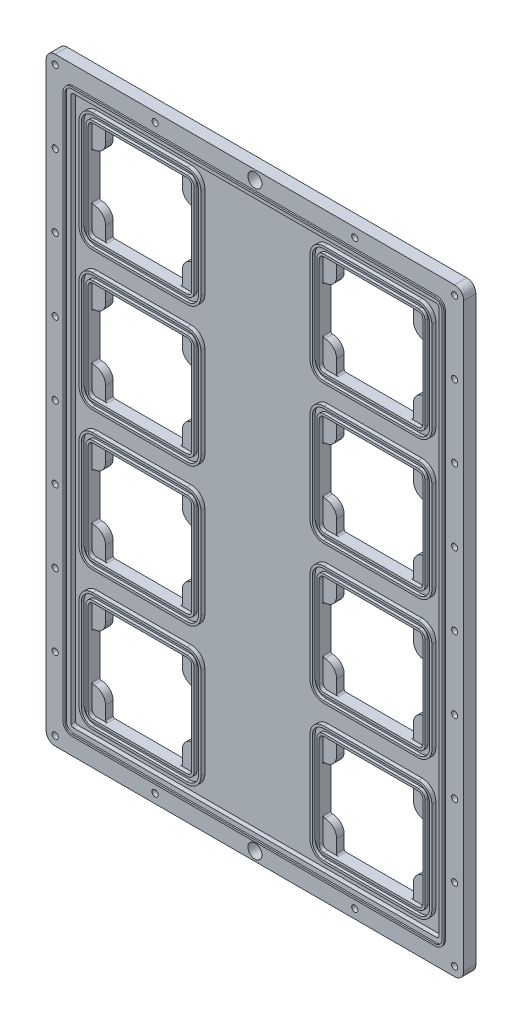
SolidWorks part; units mm, degrees
ref_plane "Front Plane" through (0, 0, 0) normal (0, 0, 1) x (1, 0, 0)
ref_plane "Top Plane" through (0, 0, 0) normal (0, 1, 0) x (1, 0, 0)
ref_plane "Right Plane" through (0, 0, 0) normal (1, 0, 0) x (0, 0, -1)
sketch "Sketch1" plane through (0, 0, 0) normal (0, 0, 1) x (1, 0, 0)
  line L1 (0, 0) -> (292.1, 0)
  line L2 (0, 0) -> (0, 419.1)
  line L3 (0, 419.1) -> (292.1, 419.1)
  line L4 (292.1, 0) -> (292.1, 419.1)
  dimension "D1" = 419.1
  dimension "D2" = 292.1
extrude "Boss-Extrude1" add sketch "Sketch1" along normal blind 8.509
sketch "Sketch4" plane through (0, 0, 8.509) normal (0, 0, 1) x (1, 0, 0)
  line L3 (0, 419.1) -> (0, 0) construction
  line L4 (6.35, 412.75) -> (285.75, 412.75) construction
  line L5 (6.35, 412.75) -> (6.35, 6.35) construction
  line L6 (6.35, 6.35) -> (285.75, 6.35) construction
  line L7 (285.75, 412.75) -> (285.75, 6.35) construction
  line L8 (292.1, 419.1) -> (0, 419.1) construction
  line L9 (292.1, 0) -> (292.1, 419.1) construction
  line L10 (0, 0) -> (292.1, 0) construction
  circle A0 centre (6.35, 6.35) radius 2.1526
  circle A1 centre (6.35, 412.75) radius 2.1526
  circle A2 centre (285.75, 412.75) radius 2.1526
  circle A3 centre (285.75, 6.35) radius 2.1526
  dimension "D5" = 4.3053
  dimension "D1" = 6.35
  dimension "D2" = 6.35
  dimension "D3" = 6.35
  dimension "D4" = 6.35
extrude "Cut-Extrude1" cut sketch "Sketch4" against normal through all
pattern_linear "LPattern2" count 8 spacing 50.8 along (0, -1, 0) of face at (287.9026, 412.75, 0) of face at (8.5026, 412.75, 0)
pattern_linear "LPattern3" count 4 spacing 69.85 along (-1, 0, 0) of face at (287.9026, 412.75, 0) of face at (287.9026, 6.35, 0)
sketch "Sketch5" plane through (0, 0, 8.509) normal (0, 0, 1) x (1, 0, 0)
  line L0 (0, 419.1) -> (0, 0) construction
  line L1 (19.05, 406.4) -> (273.05, 406.4) construction
  line L2 (12.7, 400.05) -> (12.7, 19.05) construction
  line L3 (19.05, 12.7) -> (273.05, 12.7) construction
  line L4 (279.4, 400.05) -> (279.4, 19.05) construction
  line L5 (292.1, 419.1) -> (0, 419.1) construction
  line L6 (292.1, 0) -> (292.1, 419.1) construction
  line L7 (0, 0) -> (292.1, 0) construction
  line L8 (19.05, 14.2875) -> (273.05, 14.2875) construction
  line L9 (14.2875, 400.05) -> (14.2875, 19.05) construction
  line L10 (19.05, 404.8125) -> (273.05, 404.8125) construction
  line L11 (277.8125, 400.05) -> (277.8125, 19.05) construction
  line L12 (12.827, 400.05) -> (12.827, 19.05)
  line L13 (19.05, 406.273) -> (273.05, 406.273)
  line L14 (279.273, 400.05) -> (279.273, 19.05)
  line L15 (19.05, 12.827) -> (273.05, 12.827)
  line L16 (277.9395, 400.05) -> (277.9395, 19.05)
  line L17 (19.05, 404.9395) -> (273.05, 404.9395)
  line L18 (14.1605, 400.05) -> (14.1605, 19.05)
  line L19 (19.05, 14.1605) -> (273.05, 14.1605)
  arc A0 (273.05, 12.7) -> (279.4, 19.05) centre (273.05, 19.05) ccw construction
  arc A1 (12.7, 19.05) -> (19.05, 12.7) centre (19.05, 19.05) ccw construction
  arc A2 (273.05, 406.4) -> (279.4, 400.05) centre (273.05, 400.05) cw construction
  arc A3 (19.05, 406.4) -> (12.7, 400.05) centre (19.05, 400.05) ccw construction
  arc A4 (14.2875, 19.05) -> (19.05, 14.2875) centre (19.05, 19.05) ccw construction
  arc A5 (19.05, 404.8125) -> (14.2875, 400.05) centre (19.05, 400.05) ccw construction
  arc A6 (273.05, 404.8125) -> (277.8125, 400.05) centre (273.05, 400.05) cw construction
  arc A7 (273.05, 14.2875) -> (277.8125, 19.05) centre (273.05, 19.05) ccw construction
  arc A8 (19.05, 406.273) -> (12.827, 400.05) centre (19.05, 400.05) ccw
  arc A9 (273.05, 406.273) -> (279.273, 400.05) centre (273.05, 400.05) cw
  arc A10 (273.05, 12.827) -> (279.273, 19.05) centre (273.05, 19.05) ccw
  arc A11 (12.827, 19.05) -> (19.05, 12.827) centre (19.05, 19.05) ccw
  arc A12 (273.05, 404.9395) -> (277.9395, 400.05) centre (273.05, 400.05) cw
  arc A13 (19.05, 404.9395) -> (14.1605, 400.05) centre (19.05, 400.05) ccw
  arc A14 (14.1605, 19.05) -> (19.05, 14.1605) centre (19.05, 19.05) ccw
  arc A15 (273.05, 14.1605) -> (277.9395, 19.05) centre (273.05, 19.05) ccw
  dimension "D5" = 6.35
  dimension "D1" = 12.7
  dimension "D2" = 12.7
  dimension "D3" = 12.7
  dimension "D4" = 12.7
  dimension "D6" = 1.5875
  dimension "D7" = 1.5875
  dimension "D8" = 0.127
  dimension "D9" = 0.127
  dimension "D10" = 0.127
sketch "Sketch6" plane through (0, 0, 8.509) normal (0, 0, 1) x (1, 0, 0)
  line L24 (273.05, 401.6375) -> (19.05, 401.6375)
  line L25 (274.6375, 19.05) -> (274.6375, 400.05)
  line L26 (19.05, 17.4625) -> (273.05, 17.4625)
  line L27 (17.4625, 400.05) -> (17.4625, 19.05)
  line L28 (273.05, 401.6375) -> (19.05, 401.6375)
  line L29 (274.6375, 19.05) -> (274.6375, 400.05)
  line L30 (19.05, 17.4625) -> (273.05, 17.4625)
  line L31 (17.4625, 400.05) -> (17.4625, 19.05)
  arc A20 (19.05, 401.6375) -> (17.4625, 400.05) centre (19.05, 400.05) ccw
  arc A21 (274.6375, 400.05) -> (273.05, 401.6375) centre (273.05, 400.05) ccw
  arc A22 (273.05, 17.4625) -> (274.6375, 19.05) centre (273.05, 19.05) ccw
  arc A23 (17.4625, 19.05) -> (19.05, 17.4625) centre (19.05, 19.05) ccw
  arc A24 (19.05, 401.6375) -> (17.4625, 400.05) centre (19.05, 400.05) ccw
  arc A25 (274.6375, 400.05) -> (273.05, 401.6375) centre (273.05, 400.05) ccw
  arc A26 (273.05, 17.4625) -> (274.6375, 19.05) centre (273.05, 19.05) ccw
  arc A27 (17.4625, 19.05) -> (19.05, 17.4625) centre (19.05, 19.05) ccw
  dimension "D1" = 3.175
extrude "Cut-Extrude3" cut sketch "Sketch6" against normal blind 3.175
extrude "Boss-Extrude2" add sketch "Sketch5" along normal blind 1.016 contours L12 A11 L15 A10 L14 A9 L13 A8 A15 L19 A14 L18 A13 L17 A12 L16 region at (14.9857, 404.1143, 8.509)
sketch "Sketch7" plane through (0, 0, 8.509) normal (0, 0, 1) x (1, 0, 0)
  circle A0 centre (146.05, 6.35) radius 4.9022
  circle A1 centre (146.05, 412.75) radius 4.9022
  dimension "D1" = 9.8044
extrude "Cut-Extrude4" cut sketch "Sketch7" against normal through all
fillet "Fillet1" radius 6.35 4 edges at (0, 419.1, 4.2545) (292.1, 419.1, 4.2545) (0, 0, 4.2545) (292.1, 0, 4.2545)
sketch "Sketch8" plane through (0, 0, 0) normal (0, 0, -1) x (-1, 0, 0)
  line L0 (-264.668, 370.459) -> (-264.668, 339.2678)
  line L1 (-255.27, 329.8698) -> (-255.27, 320.8782)
  line L2 (-252.4506, 318.0588) -> (-201.2442, 318.0588)
  line L3 (-198.4248, 320.8782) -> (-198.4248, 329.8698)
  line L4 (-189.0268, 339.2678) -> (-189.0268, 370.459)
  line L5 (-198.4248, 379.857) -> (-198.4248, 388.8486)
  line L6 (-201.2442, 391.668) -> (-252.4506, 391.668)
  line L7 (-255.27, 388.8486) -> (-255.27, 379.857)
  line L8 (-261.8486, 391.668) -> (-261.8486, 318.0588) construction
  line L9 (-264.668, 388.8486) -> (-189.0268, 388.8486) construction
  line L10 (-264.668, 391.668) -> (-189.0268, 391.668) construction
  line L11 (-264.668, 391.668) -> (-264.668, 318.0588) construction
  line L12 (-264.668, 318.0588) -> (-189.0268, 318.0588) construction
  line L13 (-189.0268, 391.668) -> (-189.0268, 318.0588) construction
  line L14 (-264.668, 379.857) -> (-189.0268, 379.857) construction
  line L15 (-264.668, 370.459) -> (-189.0268, 370.459) construction
  line L16 (-264.668, 339.2678) -> (-189.0268, 339.2678) construction
  line L17 (-264.668, 329.8698) -> (-189.0268, 329.8698) construction
  line L18 (-264.668, 320.8782) -> (-189.0268, 320.8782) construction
  line L19 (-255.27, 318.0588) -> (-255.27, 391.668) construction
  line L20 (-252.4506, 391.668) -> (-252.4506, 318.0588) construction
  line L21 (-201.2442, 391.668) -> (-201.2442, 318.0588) construction
  line L22 (-198.4248, 391.668) -> (-198.4248, 318.0588) construction
  line L23 (-191.8462, 318.0588) -> (-191.8462, 391.668) construction
  line L24 (-189.0268, 373.2784) -> (-264.668, 373.2784) construction
  line L27 (-201.2442, 393.7) -> (-252.4506, 393.7)
  line L28 (-257.302, 388.8486) -> (-257.302, 379.857)
  line L29 (-266.7, 370.459) -> (-266.7, 339.2678)
  line L30 (-257.302, 329.8698) -> (-257.302, 320.8782)
  line L31 (-252.4506, 316.0268) -> (-201.2442, 316.0268)
  line L32 (-196.3928, 320.8782) -> (-196.3928, 329.8698)
  line L33 (-186.9948, 339.2678) -> (-186.9948, 370.459)
  line L34 (-196.3928, 379.857) -> (-196.3928, 388.8486)
  line L35 (-285.75, 419.1) -> (-6.35, 419.1) construction
  line L36 (-292.1, 6.35) -> (-292.1, 412.75) construction
  arc A0 (-261.8486, 373.2784) -> (-255.27, 379.857) centre (-261.8486, 379.857) ccw
  arc A1 (-261.8486, 373.2784) -> (-264.668, 370.459) centre (-261.8486, 370.459) ccw
  arc A2 (-264.668, 339.2678) -> (-261.8486, 336.4484) centre (-261.8486, 339.2678) ccw
  arc A3 (-255.27, 329.8698) -> (-261.8486, 336.4484) centre (-261.8486, 329.8698) ccw
  arc A4 (-255.27, 320.8782) -> (-252.4506, 318.0588) centre (-252.4506, 320.8782) ccw
  arc A5 (-201.2442, 318.0588) -> (-198.4248, 320.8782) centre (-201.2442, 320.8782) ccw
  arc A6 (-191.8462, 336.4484) -> (-198.4248, 329.8698) centre (-191.8462, 329.8698) ccw
  arc A7 (-191.8462, 336.4484) -> (-189.0268, 339.2678) centre (-191.8462, 339.2678) ccw
  arc A8 (-189.0268, 370.459) -> (-191.8462, 373.2784) centre (-191.8462, 370.459) ccw
  arc A9 (-198.4248, 379.857) -> (-191.8462, 373.2784) centre (-191.8462, 379.857) ccw
  arc A10 (-198.4248, 388.8486) -> (-201.2442, 391.668) centre (-201.2442, 388.8486) ccw
  arc A11 (-252.4506, 391.668) -> (-255.27, 388.8486) centre (-252.4506, 388.8486) ccw
  arc A12 (-252.4506, 393.7) -> (-257.302, 388.8486) centre (-252.4506, 388.8486) ccw
  arc A13 (-261.8486, 375.3104) -> (-257.302, 379.857) centre (-261.8486, 379.857) ccw
  arc A14 (-261.8486, 375.3104) -> (-266.7, 370.459) centre (-261.8486, 370.459) ccw
  arc A15 (-266.7, 339.2678) -> (-261.8486, 334.4164) centre (-261.8486, 339.2678) ccw
  arc A16 (-257.302, 329.8698) -> (-261.8486, 334.4164) centre (-261.8486, 329.8698) ccw
  arc A17 (-257.302, 320.8782) -> (-252.4506, 316.0268) centre (-252.4506, 320.8782) ccw
  arc A18 (-201.2442, 316.0268) -> (-196.3928, 320.8782) centre (-201.2442, 320.8782) ccw
  arc A19 (-191.8462, 334.4164) -> (-196.3928, 329.8698) centre (-191.8462, 329.8698) ccw
  arc A20 (-191.8462, 334.4164) -> (-186.9948, 339.2678) centre (-191.8462, 339.2678) ccw
  arc A21 (-186.9948, 370.459) -> (-191.8462, 375.3104) centre (-191.8462, 370.459) ccw
  arc A22 (-196.3928, 379.857) -> (-191.8462, 375.3104) centre (-191.8462, 379.857) ccw
  arc A23 (-196.3928, 388.8486) -> (-201.2442, 393.7) centre (-201.2442, 388.8486) ccw
  dimension "D4" = 11.811
  dimension "D5" = 21.209
  dimension "D6" = 52.4002
  dimension "D1" = 73.6092
  dimension "D2" = 75.6412
  dimension "D3" = 2.8194
  dimension "D7" = 61.7982
  dimension "D8" = 70.7898
  dimension "D9" = 2.8194
  dimension "D10" = 9.398
  dimension "D11" = 12.2174
  dimension "D12" = 63.4238
  dimension "D13" = 66.2432
  dimension "D14" = 72.8218
  dimension "D15" = 55.2196
  dimension "D16" = 25.4
  dimension "D17" = 25.4
  dimension "D18" = 2.032
extrude "Cut-Extrude5" cut sketch "Sketch8" against normal blind 3.175
sketch "Sketch10" plane through (0, 0, 0) normal (0, 0, -1) x (-1, 0, 0)
  line L18 (-263.0805, 370.459) -> (-263.0805, 339.2678)
  line L19 (-253.6825, 329.8698) -> (-253.6825, 320.8782)
  line L20 (-252.4506, 319.6463) -> (-201.2442, 319.6463)
  line L21 (-200.0123, 320.8782) -> (-200.0123, 329.8698)
  line L22 (-190.6143, 339.2678) -> (-190.6143, 370.459)
  line L23 (-200.0123, 379.857) -> (-200.0123, 388.8486)
  line L24 (-201.2442, 390.0805) -> (-252.4506, 390.0805)
  line L25 (-253.6825, 388.8486) -> (-253.6825, 379.857)
  line L26 (-263.0805, 370.459) -> (-263.0805, 339.2678)
  line L27 (-253.6825, 329.8698) -> (-253.6825, 320.8782)
  line L28 (-252.4506, 319.6463) -> (-201.2442, 319.6463)
  line L29 (-200.0123, 320.8782) -> (-200.0123, 329.8698)
  line L30 (-190.6143, 339.2678) -> (-190.6143, 370.459)
  line L31 (-200.0123, 379.857) -> (-200.0123, 388.8486)
  line L32 (-201.2442, 390.0805) -> (-252.4506, 390.0805)
  line L33 (-253.6825, 388.8486) -> (-253.6825, 379.857)
  arc A28 (-261.8486, 371.6909) -> (-263.0805, 370.459) centre (-261.8486, 370.459) ccw
  arc A29 (-263.0805, 339.2678) -> (-261.8486, 338.0359) centre (-261.8486, 339.2678) ccw
  arc A30 (-253.6825, 329.8698) -> (-261.8486, 338.0359) centre (-261.8486, 329.8698) ccw
  arc A31 (-253.6825, 320.8782) -> (-252.4506, 319.6463) centre (-252.4506, 320.8782) ccw
  arc A32 (-201.2442, 319.6463) -> (-200.0123, 320.8782) centre (-201.2442, 320.8782) ccw
  arc A33 (-191.8462, 338.0359) -> (-200.0123, 329.8698) centre (-191.8462, 329.8698) ccw
  arc A34 (-191.8462, 338.0359) -> (-190.6143, 339.2678) centre (-191.8462, 339.2678) ccw
  arc A35 (-190.6143, 370.459) -> (-191.8462, 371.6909) centre (-191.8462, 370.459) ccw
  arc A36 (-200.0123, 379.857) -> (-191.8462, 371.6909) centre (-191.8462, 379.857) ccw
  arc A37 (-200.0123, 388.8486) -> (-201.2442, 390.0805) centre (-201.2442, 388.8486) ccw
  arc A38 (-252.4506, 390.0805) -> (-253.6825, 388.8486) centre (-252.4506, 388.8486) ccw
  arc A39 (-261.8486, 371.6909) -> (-253.6825, 379.857) centre (-261.8486, 379.857) ccw
  arc A40 (-261.8486, 371.6909) -> (-263.0805, 370.459) centre (-261.8486, 370.459) ccw
  arc A41 (-263.0805, 339.2678) -> (-261.8486, 338.0359) centre (-261.8486, 339.2678) ccw
  arc A42 (-253.6825, 329.8698) -> (-261.8486, 338.0359) centre (-261.8486, 329.8698) ccw
  arc A43 (-253.6825, 320.8782) -> (-252.4506, 319.6463) centre (-252.4506, 320.8782) ccw
  arc A44 (-201.2442, 319.6463) -> (-200.0123, 320.8782) centre (-201.2442, 320.8782) ccw
  arc A45 (-191.8462, 338.0359) -> (-200.0123, 329.8698) centre (-191.8462, 329.8698) ccw
  arc A46 (-191.8462, 338.0359) -> (-190.6143, 339.2678) centre (-191.8462, 339.2678) ccw
  arc A47 (-190.6143, 370.459) -> (-191.8462, 371.6909) centre (-191.8462, 370.459) ccw
  arc A48 (-200.0123, 379.857) -> (-191.8462, 371.6909) centre (-191.8462, 379.857) ccw
  arc A49 (-200.0123, 388.8486) -> (-201.2442, 390.0805) centre (-201.2442, 388.8486) ccw
  arc A50 (-252.4506, 390.0805) -> (-253.6825, 388.8486) centre (-252.4506, 388.8486) ccw
  arc A51 (-261.8486, 371.6909) -> (-253.6825, 379.857) centre (-261.8486, 379.857) ccw
  dimension "D1" = 1.5875
extrude "Cut-Extrude6" cut sketch "Sketch10" against normal through all
sketch "Sketch11" plane through (0, 0, 0) normal (0, 0, -1) x (-1, 0, 0)
  line L0 (-226.8474, 388.8994) -> (-226.8474, 393.7) construction
  line L1 (-261.8486, 388.8994) -> (-191.8462, 388.8994) construction
  line L2 (-261.8486, 388.8994) -> (-261.8486, 320.8274) construction
  line L3 (-261.8486, 320.8274) -> (-191.8462, 320.8274) construction
  line L4 (-191.8462, 388.8994) -> (-191.8462, 320.8274) construction
  line L5 (-201.2442, 393.7) -> (-252.4506, 393.7) construction
  line L6 (-226.8474, 320.8274) -> (-226.8474, 316.0268) construction
  line L7 (-252.4506, 316.0268) -> (-201.2442, 316.0268) construction
  line L8 (-261.8486, 354.8634) -> (-266.7, 354.8634) construction
  line L9 (-266.7, 370.459) -> (-266.7, 339.2678) construction
  line L10 (-191.8462, 354.8634) -> (-186.9948, 354.8634) construction
  line L11 (-186.9948, 339.2678) -> (-186.9948, 370.459) construction
  circle A0 centre (-261.8486, 388.8994) radius 1.1303
  circle A1 centre (-191.8462, 388.8994) radius 1.1303
  circle A2 centre (-191.8462, 320.8274) radius 1.1303
  circle A3 centre (-261.8486, 320.8274) radius 1.1303
  dimension "D3" = 2.2606
  dimension "D1" = 70.0024
  dimension "D2" = 68.072
extrude "Cut-Extrude7" cut sketch "Sketch11" against normal blind 3.9688
sketch "Sketch12" plane through (0, 0, 5.334) normal (0, 0, 1) x (1, 0, 0)
  line L0 (252.4506, 390.0805) -> (201.2442, 390.0805) construction
  line L1 (193.7893, 390.0805) -> (259.9055, 390.0805)
  line L2 (190.6143, 386.9055) -> (190.6143, 322.8213)
  line L3 (193.7893, 319.6463) -> (259.9055, 319.6463)
  line L4 (263.0805, 386.9055) -> (263.0805, 322.8213)
  line L5 (263.0805, 339.2678) -> (263.0805, 370.459) construction
  line L10 (193.7893, 391.668) -> (259.9055, 391.668)
  line L11 (264.668, 386.9055) -> (264.668, 322.8213)
  line L12 (193.7893, 318.0588) -> (259.9055, 318.0588)
  line L13 (189.0268, 386.9055) -> (189.0268, 322.8213)
  line L14 (185.8518, 386.9055) -> (185.8518, 322.8213)
  line L15 (193.7893, 314.8838) -> (259.9055, 314.8838)
  line L16 (267.843, 386.9055) -> (267.843, 322.8213)
  line L17 (193.7893, 394.843) -> (259.9055, 394.843)
  line L18 (184.2643, 386.9055) -> (184.2643, 322.8213)
  line L19 (193.7893, 313.2963) -> (259.9055, 313.2963)
  line L20 (269.4305, 386.9055) -> (269.4305, 322.8213)
  line L21 (193.7893, 396.4305) -> (259.9055, 396.4305)
  line L22 (201.2442, 319.6463) -> (252.4506, 319.6463) construction
  line L23 (190.6143, 370.459) -> (190.6143, 339.2678) construction
  arc A0 (259.9055, 319.6463) -> (263.0805, 322.8213) centre (259.9055, 322.8213) ccw
  arc A1 (190.6143, 322.8213) -> (193.7893, 319.6463) centre (193.7893, 322.8213) ccw
  arc A2 (259.9055, 390.0805) -> (263.0805, 386.9055) centre (259.9055, 386.9055) cw
  arc A3 (193.7893, 390.0805) -> (190.6143, 386.9055) centre (193.7893, 386.9055) ccw
  arc A4 (259.9055, 391.668) -> (264.668, 386.9055) centre (259.9055, 386.9055) cw
  arc A5 (259.9055, 318.0588) -> (264.668, 322.8213) centre (259.9055, 322.8213) ccw
  arc A6 (189.0268, 322.8213) -> (193.7893, 318.0588) centre (193.7893, 322.8213) ccw
  arc A7 (193.7893, 391.668) -> (189.0268, 386.9055) centre (193.7893, 386.9055) ccw
  arc A8 (185.8518, 322.8213) -> (193.7893, 314.8838) centre (193.7893, 322.8213) ccw
  arc A9 (259.9055, 314.8838) -> (267.843, 322.8213) centre (259.9055, 322.8213) ccw
  arc A10 (259.9055, 394.843) -> (267.843, 386.9055) centre (259.9055, 386.9055) cw
  arc A11 (193.7893, 394.843) -> (185.8518, 386.9055) centre (193.7893, 386.9055) ccw
  arc A12 (184.2643, 322.8213) -> (193.7893, 313.2963) centre (193.7893, 322.8213) ccw
  arc A13 (259.9055, 313.2963) -> (269.4305, 322.8213) centre (259.9055, 322.8213) ccw
  arc A14 (259.9055, 396.4305) -> (269.4305, 386.9055) centre (259.9055, 386.9055) cw
  arc A15 (193.7893, 396.4305) -> (184.2643, 386.9055) centre (193.7893, 386.9055) ccw
  dimension "D1" = 3.175
  dimension "D2" = 1.5875
  dimension "D3" = 3.175
  dimension "D4" = 1.5875
extrude "Boss-Extrude3" add sketch "Sketch12" along normal blind 2.794 contours L21 A15 L18 A12 L19 A13 L20 A14 A11 L17 A10 L16 A9 L15 A8 L14 | L10 A7 L13 A6 L12 A5 L11 A4 A3 L1 A2 L4 A0 L3 A1 L2 region at (226.8474, 390.6125, 5.334) region at (187.8957, 392.7991, 5.334)
extrude "Boss-Extrude4" add sketch "Sketch12<3>" along normal blind 0.7937 contours L17 A11 L14 A8 L15 A9 L16 A10 A7 L10 A4 L11 A5 L12 A6 L13 region at (188.9865, 391.7083, 5.334)
sketch "Sketch12<3>" plane through (0, 0, 5.334) normal (0, 0, 1) x (1, 0, 0) same geometry as "Sketch12"
pattern_linear "LPattern1" count 2 spacing 161.5948 along (-1, 0, 0) count 4 spacing 96.8756 along (0, -1, 0) of "Cut-Extrude6", "Cut-Extrude5", "Cut-Extrude7", "Boss-Extrude3", "Boss-Extrude4"
